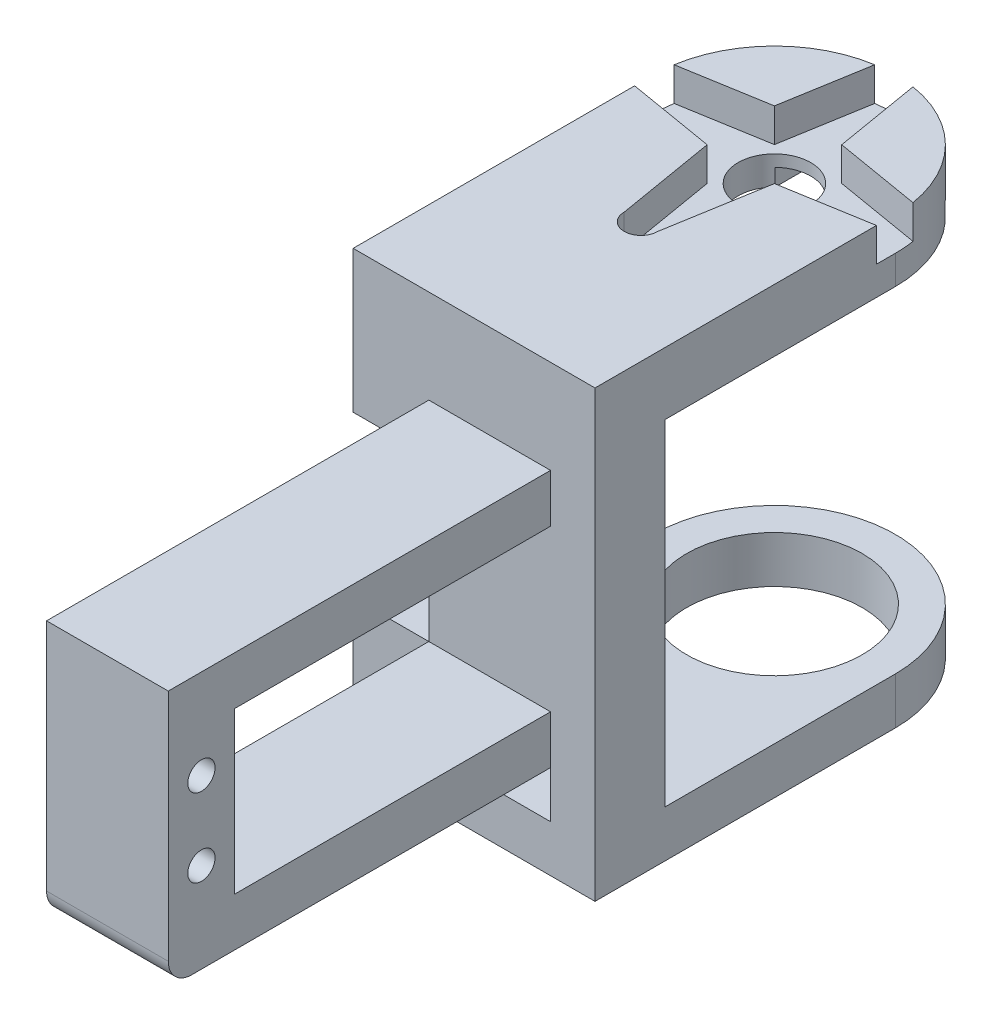
SolidWorks part; units mm, degrees
note: The reader was unsure of these and kept them because the rebuilt part matched: shared geometry of "Sketch6<3>", "Sketch9<3>".
ref_plane "Front Plane" through (0, 0, 0) normal (0, 0, 1) x (1, 0, 0)
ref_plane "Top Plane" through (0, 0, 0) normal (0, 1, 0) x (1, 0, 0)
ref_plane "Right Plane" through (0, 0, 0) normal (1, 0, 0) x (0, 0, -1)
sketch "Sketch1" plane through (0, 0, 0) normal (0, 0, 1) x (1, 0, 0)
  line L0 (-15.5, -28.5) -> (-8.5, -28.5) construction
  line L1 (15.5, -28.5) -> (-15.5, -28.5)
  line L2 (15.5, -28.5) -> (15.5, 28.5)
  line L3 (15.5, 28.5) -> (-15.5, 28.5)
  line L4 (-15.5, -28.5) -> (-15.5, -10.3)
  line L5 (15.5, -28.5) -> (-15.5, 28.5) construction
  line L6 (15.5, 28.5) -> (-15.5, -28.5) construction
  line L7 (-8.5, -28.5) -> (-8.5, -22.5) construction
  line L8 (-15.5, -28.5) -> (-15.5, -10.3) construction
  line L9 (-8.5, -22.5) -> (9.8, -22.5)
  line L10 (-8.5, -22.5) -> (-8.5, -16.5)
  line L11 (-8.5, -16.5) -> (9.8, -16.5)
  line L12 (9.8, -22.5) -> (9.8, -16.5)
  line L13 (-15.5, 10.3) -> (-15.5, 28.5)
  line L14 (-15.5, -10.3) -> (-5.8, -10.3)
  line L16 (-15.5, 10.3) -> (-5.8, 10.3)
  line L17 (-5.8, -10.3) -> (-5.8, 10.3)
  point P0 (0, 0)
  dimension "D1" = 31
  dimension "D2" = 57
  dimension "D3" = 7
  dimension "D4" = 6
  dimension "D5" = 18.3
  dimension "D6" = 6
  dimension "D7" = 18.2
  dimension "D8" = 20.6
  dimension "D9" = 9.7
extrude "Boss-Extrude1" add sketch "Sketch1" along normal blind 9
sketch "Sketch2" plane through (0, 0, 9) normal (0, 0, 1) x (1, 0, 0)
  line L1 (-5.8, -10.3) -> (9.8, -10.3)
  line L2 (-5.8, -10.3) -> (-5.8, -16.5)
  line L3 (-5.8, -16.5) -> (9.8, -16.5)
  line L4 (9.8, -10.3) -> (9.8, -16.5)
  line L5 (-5.8, 10.3) -> (9.8, 10.3)
  line L6 (-5.8, 10.3) -> (-5.8, 16.5)
  line L7 (-5.8, 16.5) -> (9.8, 16.5)
  line L8 (9.8, 10.3) -> (9.8, 16.5)
  dimension "D1" = 6.2
extrude "Boss-Extrude2" add sketch "Sketch2" along normal blind 49
sketch "Sketch3" plane through (0, 10.3, 0) normal (0, -1, 0) x (1, 0, 0)
  line L0 (9.8, 58) -> (9.8, 9) construction
  line L1 (-5.8, 58) -> (9.8, 58)
  line L2 (-5.8, 58) -> (-5.8, 49.5)
  line L3 (-5.8, 49.5) -> (9.8, 49.5)
  line L4 (9.8, 58) -> (9.8, 49.5)
  dimension "D1" = 8.5
extrude "Boss-Extrude3" add sketch "Sketch3" along normal blind 20.7
fillet "Fillet3" radius 3 1 edges at (2, -16.5, 58)
sketch "Sketch4" plane through (0, 0, 0) normal (0, 0, -1) x (-1, 0, 0)
  line L0 (15.5, 28.5) -> (15.5, 10.3) construction
  line L1 (-15.5, 28.5) -> (15.5, 28.5)
  line L2 (-15.5, 28.5) -> (-15.5, 20.5)
  line L3 (-15.5, 20.5) -> (15.5, 20.5)
  line L4 (15.5, 28.5) -> (15.5, 20.5)
  line L5 (15.5, -10.3) -> (15.5, -28.5) construction
  line L6 (-15.5, -28.5) -> (15.5, -28.5)
  line L7 (-15.5, -28.5) -> (-15.5, -22.5)
  line L8 (-15.5, -22.5) -> (15.5, -22.5)
  line L9 (15.5, -28.5) -> (15.5, -22.5)
  dimension "D1" = 8
  dimension "D2" = 6
extrude "Boss-Extrude4" add sketch "Sketch4" along normal blind 45
sketch "Sketch6" plane through (0, -28.5, 0) normal (0, -1, 0) x (1, 0, 0)
  line L0 (0, 0) -> (0, -29.5) construction
  line L1 (15.5, 9) -> (15.5, -45) construction
  line L2 (-15.5, -29.5) -> (-15.5, -45)
  line L3 (-15.5, -45) -> (15.5, -45)
  line L4 (15.5, -45) -> (-15.5, -45) construction
  line L5 (15.5, -45) -> (15.5, -29.5)
  arc A0 (15.5, -29.5) -> (-15.5, -29.5) centre (0, -29.5) cw
  circle A1 centre (0, -29.5) radius 11.25
  line M2 (-15.5, 9) -> (-15.5, -45)
  line M3 (-15.5, -45) -> (15.5, -45)
  line M4 (15.5, -45) -> (15.5, 9)
  dimension "D2" = 15.5
  dimension "D3" = 22.5
  dimension "D1" = 29.5
extrude "Cut-Extrude1" cut sketch "Sketch6" against normal through all contours A0 L3 M4 | A0 M3 M2
extrude "Cut-Extrude2" cut sketch "Sketch6<3>" against normal blind 6
sketch "Sketch6<3>" plane through (0, -28.5, 0) normal (0, -1, 0) x (1, 0, 0) same geometry as "Sketch6"
sketch "Sketch7" plane through (0, 28.5, 0) normal (0, 1, 0) x (1, 0, 0)
  line L0 (0, 0) -> (0, 29.5) construction
  line L1 (0, 29.5) -> (0, 12.4) construction
  line L2 (0, 29.5) -> (17.1, 29.5) construction
  line L3 (0, 29.5) -> (0, 46.6) construction
  line L4 (0, 29.5) -> (-17.1, 29.5) construction
  line L5 (-17.1, 31.65) -> (-4.3134, 33.8134)
  line L6 (-4.3134, 33.8134) -> (-2.15, 46.6)
  line L7 (-4.3134, 25.1866) -> (-2.15, 12.4)
  line L8 (-17.1, 27.35) -> (-4.3134, 25.1866)
  line L9 (4.3134, 25.1866) -> (2.15, 12.4)
  line L10 (17.1, 27.35) -> (4.3134, 25.1866)
  line L11 (17.1, 31.65) -> (4.3134, 33.8134)
  line L12 (4.3134, 33.8134) -> (2.15, 46.6)
  arc A1 (-2.15, 12.4) -> (2.15, 12.4) centre (0, 12.4) ccw
  arc A2 (2.15, 46.6) -> (-2.15, 46.6) centre (0, 46.6) ccw
  arc A3 (17.1, 27.35) -> (17.1, 31.65) centre (17.1, 29.5) ccw
  arc A4 (-17.1, 31.65) -> (-17.1, 27.35) centre (-17.1, 29.5) ccw
  arc A5 (4.3134, 25.1866) -> (6.1, 29.5) centre (0, 29.5) ccw construction
  dimension "D4" = 4.3
  dimension "D8" = 4.3
  dimension "D9" = 4.3
  dimension "D10" = 4.3
  dimension "D11" = 12.2
  dimension "D1" = 29.5
  dimension "D3" = 17.1
  dimension "D5" = 17.1
  dimension "D6" = 17.1
  dimension "D7" = 17.1
  dimension "D12" = 24.1142
extrude "Cut-Extrude3" cut sketch "Sketch7" against normal blind 4.3
sketch "Sketch9" plane through (0, 20.5, 0) normal (0, -1, 0) x (1, 0, 0)
  line L0 (0, 0) -> (0, -29.5) construction
  line L1 (15.5, 0) -> (-15.5, 0) construction
  line L2 (3.25, -29.5) -> (-3.25, -29.5) construction
  line L3 (-3.25, -29.5) -> (-3.25, -32.8257) construction
  line L4 (3.25, -29.5) -> (3.25, -32.8257) construction
  line L5 (-3.25, -32.8257) -> (-3.25, -44.6554)
  line L6 (3.25, -32.8257) -> (3.25, -44.6554)
  circle A0 centre (0, -29.5) radius 4.65
  arc A1 (-15.5, -29.5) -> (15.5, -29.5) centre (0, -29.5) ccw construction
  dimension "D2" = 9.3
  dimension "D1" = 29.5
  dimension "D3" = 3.25
extrude "Cut-Extrude4" cut sketch "Sketch9" against normal blind 2.2 contours A0 L5 L4 L6
extrude "Cut-Extrude5" cut sketch "Sketch9<3>" against normal blind 8 contours A0
sketch "Sketch9<3>" plane through (0, 20.5, 0) normal (0, -1, 0) x (1, 0, 0) same geometry as "Sketch9"
sketch "Sketch10" plane through (-5.8, 0, 0) normal (-1, 0, 0) x (0, 0, 1)
  line L0 (0, 0) -> (4.5, 0) construction
  line L1 (4.5, 0) -> (4.5, 5) construction
  line L2 (4.5, 0) -> (58, 0) construction
  line L3 (58, 16.5) -> (58, -13.5) construction
  line L4 (58, 0) -> (53.75, 0) construction
  line L5 (53.75, 0) -> (53.75, 5) construction
  circle A0 centre (4.5, 5) radius 1.75
  circle A1 centre (4.5, -5) radius 1.75
  circle A2 centre (53.75, 5) radius 1.75
  circle A3 centre (53.75, -5) radius 1.75
  dimension "D3" = 3.5
  dimension "D6" = 3.5
  dimension "D1" = 5
  dimension "D2" = 4.5
  dimension "D4" = 4.25
  dimension "D5" = 5
extrude "Cut-Extrude6" cut sketch "Sketch10" against normal blind 18
